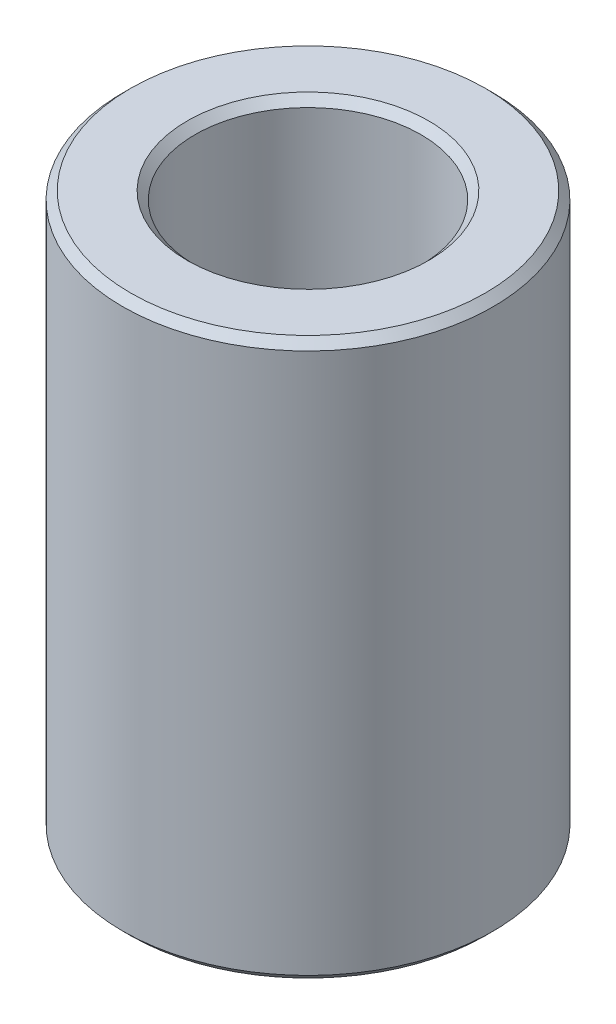
SolidWorks part; units mm, degrees
ref_plane "Front Plane" through (0, 0, 0) normal (0, 0, 1) x (1, 0, 0)
ref_plane "Top Plane" through (0, 0, 0) normal (0, 1, 0) x (1, 0, 0)
ref_plane "Right Plane" through (0, 0, 0) normal (1, 0, 0) x (0, 0, -1)
sketch "Sketch1" plane through (0, 0, 0) normal (0, 1, 0) x (1, 0, 0)
  circle A0 centre (0, 0) radius 42.5
  dimension "SLEEVE_OD" = 85
extrude "Boss-Extrude1" add sketch "Sketch1" along normal blind 127.7027
sketch "Sketch2" plane through (0, 0, 0) normal (0, 1, 0) x (1, 0, 0)
  circle A0 centre (0, 0) radius 25.9184
  dimension "BORE_D" = 51.8368
extrude "Cut-Extrude1" cut sketch "Sketch2" along normal through all
chamfer "Chamfer1" distance 1.8117 angle 45 4 edges at (0, 127.7027, 25.9184) (0, 0, 25.9184) (0, 0, 42.5) (0, 127.7027, 42.5)
